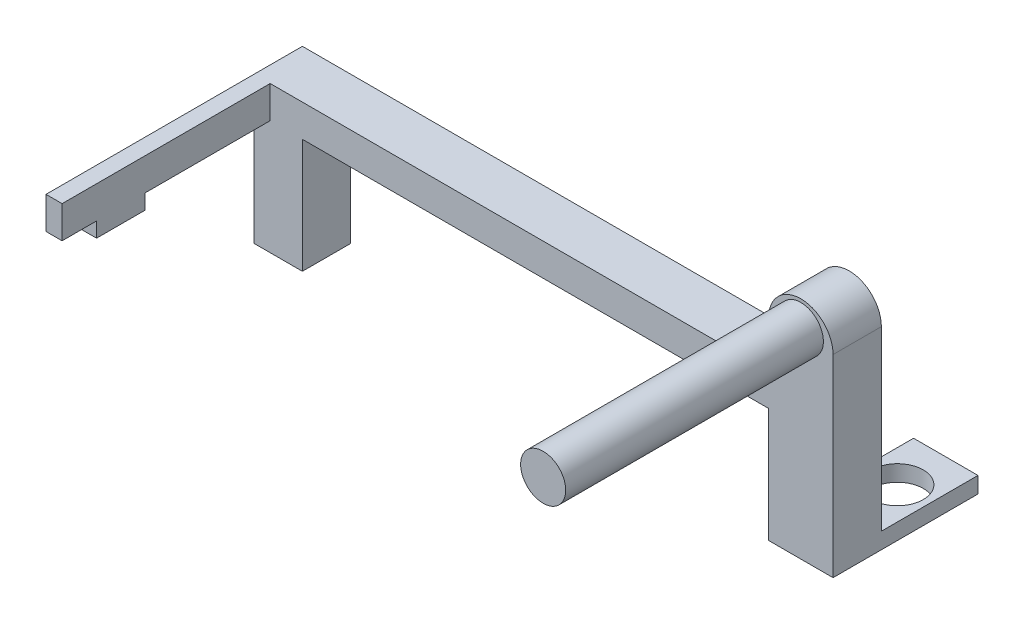
SolidWorks part; units mm, degrees
ref_plane "Front Plane" through (0, 0, 0) normal (0, 0, 1) x (1, 0, 0)
ref_plane "Top Plane" through (0, 0, 0) normal (0, 1, 0) x (1, 0, 0)
ref_plane "Right Plane" through (0, 0, 0) normal (1, 0, 0) x (0, 0, -1)
sketch "Sketch1" plane through (0, 0, 0) normal (0, 0, 1) x (1, 0, 0)
  line L1 (-3.4341, 3.4024) -> (0.5659, 3.4024)
  line L2 (-3.4341, 3.4024) -> (-3.4341, -10.5976)
  line L3 (-3.4341, -10.5976) -> (0.5659, -10.5976)
  line L4 (0.5659, 3.4024) -> (0.5659, -10.5976)
  dimension "D1" = 14
  dimension "D2" = 4
extrude "Boss-Extrude1" add sketch "Sketch1" along normal blind 3
sketch "Sketch2" plane through (0, 0, 0) normal (0, 0, -1) x (-1, 0, 0)
  line L0 (1.4341, -10.5976) -> (1.4341, 1.8024) construction
  line L1 (3.4341, -10.5976) -> (-0.5659, -10.5976) construction
  circle A0 centre (1.4341, 1.8024) radius 1.4
  dimension "D2" = 2.8
  dimension "D1" = 12.4
extrude "Boss-Extrude2" add sketch "Sketch2" along normal blind 16
fillet "Fillet1" 2 edges at (-3.4341, 3.4024, 1.5) (0.5659, 3.4024, 1.5) type full round first side face at (-3.4341, -3.5976, 1.5) second side face at (0.5659, -3.5976, 1.5) middle face at (-1.4341, 3.4024, 1.5)
sketch "Sketch3" plane through (0, 0, 3) normal (0, 0, 1) x (1, 0, 0)
  line L0 (-3.4341, 1.4024) -> (-3.4341, -10.5976) construction
  line L1 (-3.4341, -9.5976) -> (0.5659, -9.5976)
  line L2 (-3.4341, -9.5976) -> (-3.4341, -10.5976)
  line L3 (-3.4341, -10.5976) -> (0.5659, -10.5976)
  line L4 (0.5659, -9.5976) -> (0.5659, -10.5976)
  dimension "D1" = 1
extrude "Boss-Extrude4" add sketch "Sketch3" along normal blind 6
sketch "Sketch5" plane through (0, -9.5976, 0) normal (0, 1, 0) x (1, 0, 0)
  line L0 (-3.4341, -6) -> (0.5659, -6) construction
  line L1 (-3.4341, -9) -> (-3.4341, -3) construction
  line L2 (0.5659, -9) -> (0.5659, -3) construction
  line L3 (-1.4341, -9) -> (-1.4341, -3) construction
  line L4 (0.5659, -9) -> (-3.4341, -9) construction
  line L5 (0.5659, -3) -> (-3.4341, -3) construction
sketch "Sketch6" plane through (0, -9.5976, 0) normal (0, 1, 0) x (1, 0, 0)
  line L0 (-3.4341, -6) -> (0.5659, -6) construction
  circle A0 centre (-1.4341, -6) radius 1.6
  dimension "D1" = 3.2
extrude "Cut-Extrude2" cut sketch "Sketch6" against normal blind 6
sketch "Sketch7" plane through (-3.4341, 0, 0) normal (-1, 0, 0) x (0, 0, 1)
  line L0 (0, 1.4024) -> (0, -10.5976) construction
  line L1 (0, -1.4976) -> (3, -1.4976)
  line L2 (0, -1.4976) -> (0, -3.4976)
  line L3 (0, -3.4976) -> (3, -3.4976)
  line L4 (3, -1.4976) -> (3, -3.4976)
  line L5 (3, 1.4024) -> (3, -9.5976) construction
  line L6 (9, -10.5976) -> (0, -10.5976) construction
  dimension "D1" = 7.1
  dimension "D2" = 2
extrude "Boss-Extrude5" add sketch "Sketch7" along normal blind 30.95
sketch "Sketch8" plane through (-34.3841, 0, 0) normal (-1, 0, 0) x (0, 0, 1)
  line L1 (0, -1.4976) -> (3, -1.4976)
  line L2 (0, -1.4976) -> (0, -3.4976)
  line L3 (0, -3.4976) -> (3, -3.4976)
  line L4 (3, -1.4976) -> (3, -3.4976)
extrude "Boss-Extrude6" add sketch "Sketch8" along normal blind 1
sketch "Sketch9" plane through (0, 0, 0) normal (0, 0, -1) x (-1, 0, 0)
  line L0 (35.3841, -3.4976) -> (3.4341, -3.4976) construction
  line L1 (35.3841, -1.4976) -> (34.3841, -1.4976)
  line L2 (35.3841, -1.4976) -> (35.3841, -3.4976)
  line L3 (35.3841, -3.4976) -> (34.3841, -3.4976)
  line L4 (34.3841, -1.4976) -> (34.3841, -3.4976)
  dimension "D1" = 1
extrude "Boss-Extrude7" add sketch "Sketch9" along normal blind 3
sketch "Sketch10" plane through (0, 0, -3) normal (0, 0, -1) x (-1, 0, 0)
  line L0 (34.3841, -3.4976) -> (35.3841, -3.4976) construction
  line L1 (34.3841, -1.4976) -> (35.3841, -1.4976)
  line L2 (34.3841, -1.4976) -> (34.3841, -3.4976)
  line L3 (34.3841, -3.4976) -> (35.3841, -3.4976)
  line L4 (35.3841, -1.4976) -> (35.3841, -3.4976)
  line L5 (35.3841, -3.4976) -> (35.3841, -1.4976) construction
extrude "Boss-Extrude8" add sketch "Sketch10" along normal blind 5.92
sketch "Sketch11" plane through (0, 0, -8.92) normal (0, 0, -1) x (-1, 0, 0)
  line L1 (34.3841, -1.4976) -> (35.3841, -1.4976)
  line L2 (34.3841, -1.4976) -> (34.3841, -3.4976)
  line L3 (34.3841, -3.4976) -> (35.3841, -3.4976)
  line L4 (35.3841, -1.4976) -> (35.3841, -3.4976)
extrude "Boss-Extrude9" add sketch "Sketch11" along normal blind 4
sketch "Sketch12" plane through (0, -3.4976, 0) normal (0, -1, 0) x (1, 0, 0)
  line L0 (-35.3841, 3) -> (-35.3841, -7.78) construction
  line L1 (-35.3841, -12.92) -> (-35.3841, 3) construction
  line L2 (-34.3841, -12.92) -> (-34.3841, 0) construction
  line L3 (-35.3841, -7.78) -> (-34.3841, -7.78)
  line L4 (-35.3841, -7.78) -> (-35.3841, -10.78)
  line L5 (-35.3841, -10.78) -> (-34.3841, -10.78)
  line L6 (-34.3841, -7.78) -> (-34.3841, -10.78)
  dimension "D1" = 10.78
  dimension "D2" = 3
extrude "Boss-Extrude14" add sketch "Sketch12" along normal blind 0.93
sketch "Sketch13" plane through (0, -3.4976, 0) normal (0, -1, 0) x (1, 0, 0)
  line L0 (-34.3841, 0) -> (-3.4341, 0) construction
  line L1 (-35.3841, 3) -> (-32.3841, 3)
  line L2 (-35.3841, 3) -> (-35.3841, 0)
  line L3 (-35.3841, 0) -> (-32.3841, 0)
  line L4 (-32.3841, 3) -> (-32.3841, 0)
  dimension "D1" = 3
extrude "Boss-Extrude15" add sketch "Sketch13" along normal blind 7.1
ref_plane "Plane1" through (0, 0, -48.1934) normal (0, 0, 1) x (1, 0, 0)
mirror "Mirror1" about plane through (0, 0, -48.1934) normal (0, 0, 1) of bodies 117
delete or keep bodies "Body-Delete/Keep 1" type delete bodies bodies 117
